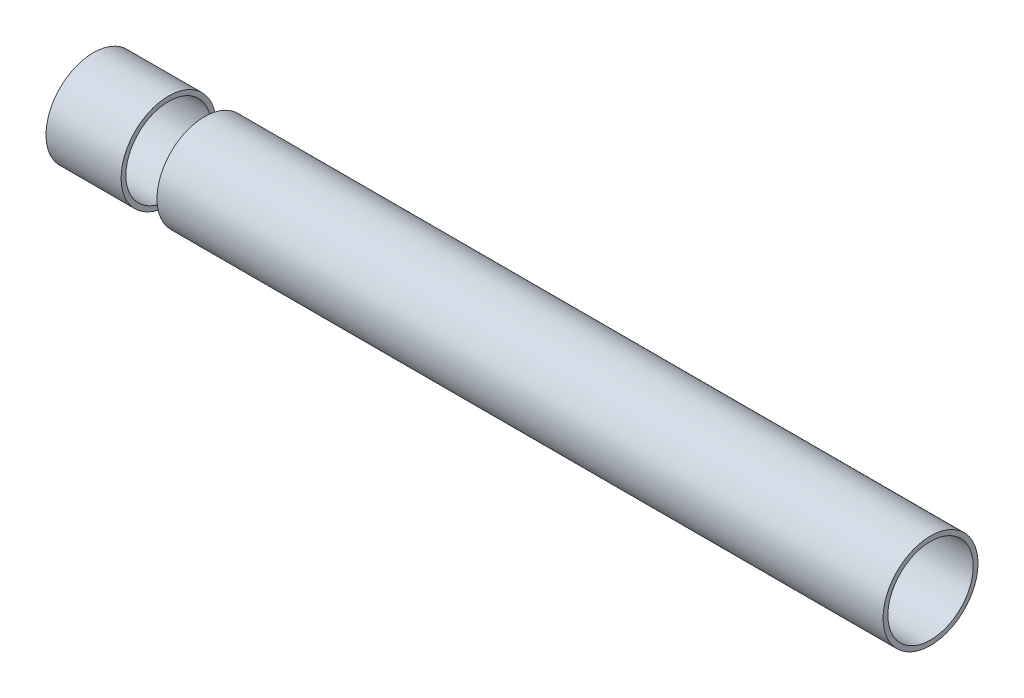
SolidWorks part; units mm, degrees
material "PC High Viscosity"
ref_plane "Front Plane" through (0, 0, 0) normal (0, 0, 1) x (1, 0, 0)
ref_plane "Top Plane" through (0, 0, 0) normal (0, 1, 0) x (1, 0, 0)
ref_plane "Right Plane" through (0, 0, 0) normal (1, 0, 0) x (0, 0, -1)
sketch "Sketch1" plane through (0, 0, 0) normal (1, 0, 0) x (0, 0, -1)
  circle A0 centre (0, 0) radius 15.875
  dimension "D1" = 31.75
extrude "Extrude-Thin1" add sketch "Sketch1" along normal mid plane 280.0385 thin thin type one direction reverse wall 1.5875
sketch "Sketch2" plane through (0, 0, 0) normal (0, 1, 0) x (1, 0, 0)
  line L0 (140.0193, 15.875) -> (-140.0193, 15.875) construction
  line L1 (-102.8953, 15.875) -> (-114.8953, 15.875)
  line L2 (-102.8953, 15.875) -> (-102.8953, -15.875)
  line L3 (-102.8953, -15.875) -> (-114.8953, -15.875)
  line L4 (-114.8953, 15.875) -> (-114.8953, -15.875)
  line L5 (-140.0193, -15.875) -> (140.0193, -15.875) construction
  line L6 (-140.0193, 14.2875) -> (-140.0193, -14.2875) construction
  dimension "D1" = 37.1239
  dimension "D2" = 12
extrude "Cut-Extrude1" cut sketch "Sketch2" against normal through all both and the other way through all
equation "\"D2@Sketch2\"=12mm"
